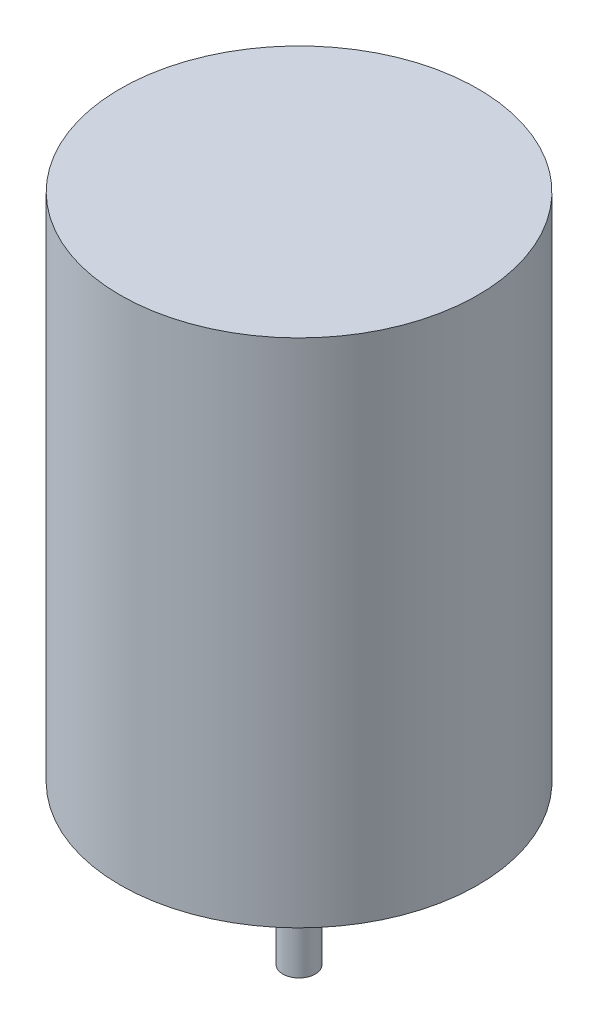
SolidWorks part; units mm, degrees
ref_plane "Front" through (0, 0, 0) normal (0, 0, 1) x (1, 0, 0)
ref_plane "Top" through (0, 0, 0) normal (0, 1, 0) x (1, 0, 0)
ref_plane "Right" through (0, 0, 0) normal (1, 0, 0) x (0, 0, -1)
sketch "Sketch1" plane through (0, 0, 0) normal (0, 1, 0) x (1, 0, 0)
  circle A0 centre (0, 0) radius 17.5
  circle A1 centre (0, 0) radius 12.5
  circle A2 centre (0, 0) radius 5
  circle A3 centre (0, 0) radius 1.5875
  circle A4 centre (0, -12.5) radius 1.5
  circle A5 centre (0, 12.5) radius 1.5
  dimension "D1" = 35
  dimension "D2" = 25
  dimension "D3" = 10
  dimension "D4" = 3.175
  dimension "D5" = 3
  dimension "D6" = 3
extrude "Boss-Extrude1" add sketch "Sketch1" along normal blind 50 contours A0
extrude "Boss-Extrude2" add sketch "Sketch1<3>" against normal blind 2 contours A2
sketch "Sketch1<3>" plane through (0, 0, 0) normal (0, 1, 0) x (1, 0, 0) same geometry as "Sketch1"
extrude "Boss-Extrude3" add sketch "Sketch1<4>" against normal blind 13.5 from surface contours A3 starting at face at (0, -2, 5)
sketch "Sketch1<4>" plane through (0, 0, 0) normal (0, 1, 0) x (1, 0, 0) same geometry as "Sketch1"
extrude "Cut-Extrude1" cut sketch "Sketch1<5>" along normal blind 13.5 contours A4 | A5
sketch "Sketch1<5>" plane through (0, 0, 0) normal (0, 1, 0) x (1, 0, 0) same geometry as "Sketch1"
